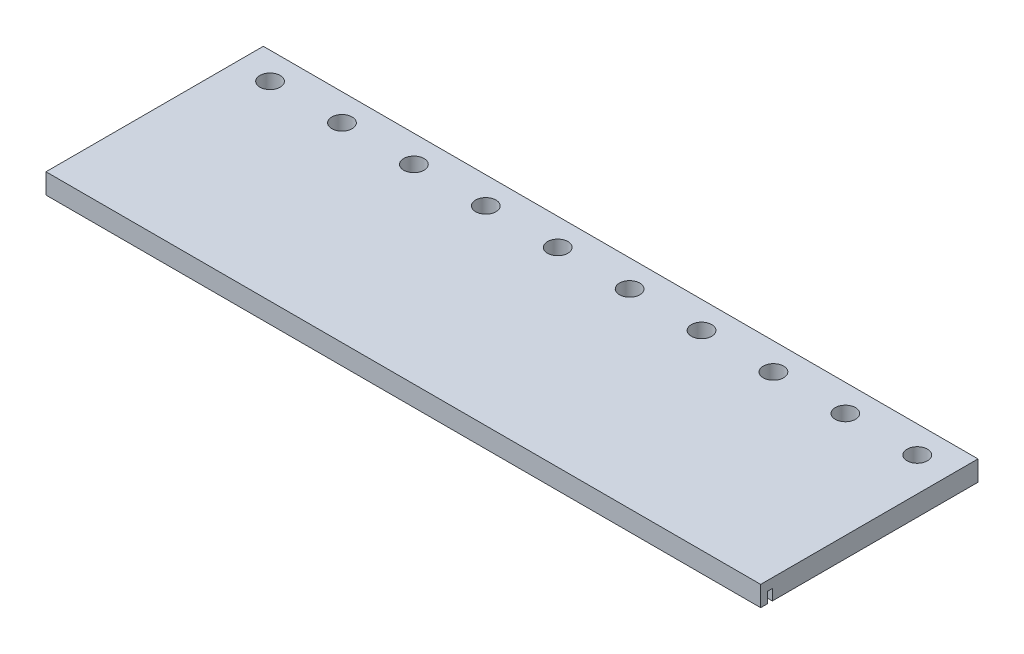
SolidWorks part; units mm, degrees
ref_plane "Front Plane" through (0, 0, 0) normal (0, 0, 1) x (1, 0, 0)
ref_plane "Top Plane" through (0, 0, 0) normal (0, 1, 0) x (1, 0, 0)
ref_plane "Right Plane" through (0, 0, 0) normal (1, 0, 0) x (0, 0, -1)
sketch "Sketch1" plane through (0, 0, 0) normal (0, 1, 0) x (1, 0, 0)
  line L1 (336.55, 102.3366) -> (-336.55, 102.3366)
  line L2 (336.55, 102.3366) -> (336.55, -102.3366)
  line L3 (336.55, -102.3366) -> (-336.55, -102.3366)
  line L4 (-336.55, 102.3366) -> (-336.55, -102.3366)
  line L5 (336.55, 102.3366) -> (-336.55, -102.3366) construction
  line L6 (336.55, -102.3366) -> (-336.55, 102.3366) construction
  point P0 (0, 0)
  dimension "D1" = 673.1
  dimension "D2" = 204.6732
extrude "Boss-Extrude1" add sketch "Sketch1" along normal mid plane 19.05
sketch "Sketch2" plane through (0, 9.525, 0) normal (0, 1, 0) x (1, 0, 0)
  line L0 (0, 0) -> (0, 102.3366) construction
  line L1 (336.55, 102.3366) -> (-336.55, 102.3366) construction
  line L2 (-304.8, 76.9304) -> (-25.4, 76.9304) construction
  line L4 (304.8, 101.2138) -> (304.8, 50.7401) construction
  line L5 (-336.55, -102.3366) -> (336.55, -102.3366) construction
  circle A2 centre (-304.8, 76.9304) radius 9.5846
  circle A12 centre (-237.0709, 76.9304) radius 9.5846
  circle A13 centre (-169.3418, 76.9304) radius 9.5846
  circle A14 centre (-101.6127, 76.9304) radius 9.5846
  circle A15 centre (-33.8836, 76.9304) radius 9.5846
  circle A16 centre (33.8455, 76.9304) radius 9.5846
  circle A17 centre (101.5746, 76.9304) radius 9.5846
  circle A18 centre (169.3037, 76.9304) radius 9.5846
  circle A19 centre (237.0328, 76.9304) radius 9.5846
  circle A20 centre (304.7619, 76.9304) radius 9.5846
  dimension "D2" = 179.267
  dimension "D3" = 304.8
  dimension "D1" = 19.1692
  dimension "D5" = 10
  dimension "D4" = 304.8
extrude "Cut-Extrude1" cut sketch "Sketch2" against normal through all both and the other way through all
sketch "Sketch4" plane through (0, -9.525, 0) normal (0, -1, 0) x (1, 0, 0)
  line L1 (336.55, 96.0355) -> (-336.55, 96.0355)
  line L2 (336.55, 96.0355) -> (336.55, 91.3365)
  line L3 (336.55, 91.3365) -> (-336.55, 91.3365)
  line L4 (-336.55, 96.0355) -> (-336.55, 91.3365)
  line L5 (-336.55, -102.3366) -> (-336.55, 102.3366) construction
  line L6 (336.55, 102.3366) -> (336.55, -102.3366) construction
  line L7 (-336.55, 102.3366) -> (336.55, 102.3366) construction
  dimension "D1" = 6.3011
  dimension "D2" = 4.699
extrude "Cut-Extrude2" cut sketch "Sketch4" against normal blind 10.16
sketch "Sketch7" plane through (0, -9.525, 0) normal (0, -1, 0) x (1, 0, 0)
  line L0 (-323.0562, -34.2921) -> (323.0562, -34.2921) construction
  line L3 (-323.0562, -26.2911) -> (323.0562, -26.2911)
  line L4 (-323.0562, -42.2931) -> (323.0562, -42.2931)
  line L5 (0, 0) -> (0, -34.2921) construction
  line L6 (-336.55, 102.3366) -> (336.55, 102.3366) construction
  arc A0 (-323.0562, -26.2911) -> (-323.0562, -42.2931) centre (-323.0562, -34.2921) ccw
  arc A1 (323.0562, -42.2931) -> (323.0562, -26.2911) centre (323.0562, -34.2921) ccw
  point P6 (0, -34.2921)
  dimension "D1" = 16.002
  dimension "D2" = 646.1125
  dimension "D3" = 136.6287
extrude "Cut-Extrude5" cut sketch "Sketch7" against normal blind 7.9375
